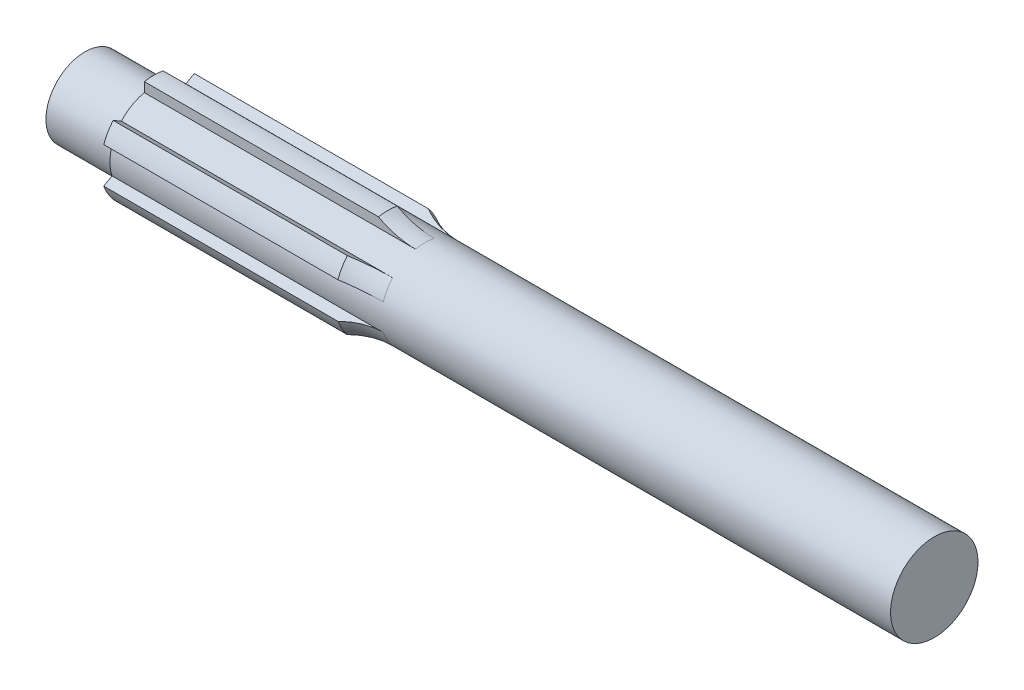
SolidWorks part; units mm, degrees
material "Gray Cast Iron"
ref_plane "Front Plane" through (0, 0, 0) normal (0, 0, 1) x (1, 0, 0)
ref_plane "Top Plane" through (0, 0, 0) normal (0, 1, 0) x (1, 0, 0)
ref_plane "Right Plane" through (0, 0, 0) normal (1, 0, 0) x (0, 0, -1)
sketch "Sketch1" plane through (0, 0, 0) normal (1, 0, 0) x (0, 0, -1)
  circle A0 centre (0, 0) radius 12.5
  dimension "D1" = 25
extrude "Boss-Extrude1" add sketch "Sketch1" along normal blind 22
sketch "Sketch2" plane through (22, 0, 0) normal (1, 0, 0) x (0, 0, -1)
  line L0 (0, -1000) -> (0, 49000) construction
  line L1 (-13.3427, -4.2393) -> (-15.9914, -5.7685)
  line L3 (-3, -13.6748) -> (-3, -16.7332)
  line L5 (3, -13.6748) -> (3, -16.7332)
  line L6 (-3, -13.6748) -> (3, -16.7332) construction
  line L7 (-3, -16.7332) -> (3, -13.6748) construction
  line L8 (-10.3427, -9.4355) -> (-12.9914, -10.9647)
  line L9 (-10.3427, 9.4355) -> (-12.9914, 10.9647)
  line L10 (-13.3427, 4.2393) -> (-15.9914, 5.7685)
  line L11 (3, 13.6748) -> (3, 16.7332)
  line L12 (-3, 13.6748) -> (-3, 16.7332)
  line L13 (13.3427, 4.2393) -> (15.9914, 5.7685)
  line L14 (10.3427, 9.4355) -> (12.9914, 10.9647)
  line L15 (10.3427, -9.4355) -> (12.9914, -10.9647)
  line L16 (13.3427, -4.2393) -> (15.9914, -5.7685)
  arc A0 (-3, 13.6748) -> (-10.3427, 9.4355) centre (0, 0) ccw
  arc A1 (3, 16.7332) -> (-3, 16.7332) centre (0, 0) ccw
  arc A2 (10.3427, 9.4355) -> (3, 13.6748) centre (0, 0) ccw
  arc A3 (15.9914, 5.7685) -> (12.9914, 10.9647) centre (0, 0) ccw
  arc A4 (13.3427, -4.2393) -> (13.3427, 4.2393) centre (0, 0) ccw
  arc A5 (12.9914, -10.9647) -> (15.9914, -5.7685) centre (0, 0) ccw
  arc A6 (3, -13.6748) -> (10.3427, -9.4355) centre (0, 0) ccw
  arc A7 (-3, -16.7332) -> (3, -16.7332) centre (0, 0) ccw
  arc A8 (-10.3427, -9.4355) -> (-3, -13.6748) centre (0, 0) ccw
  arc A9 (-15.9914, -5.7685) -> (-12.9914, -10.9647) centre (0, 0) ccw
  arc A10 (-13.3427, 4.2393) -> (-13.3427, -4.2393) centre (0, 0) ccw
  arc A11 (-12.9914, 10.9647) -> (-15.9914, 5.7685) centre (0, 0) ccw
  point P4 (0, -15.204)
  point P33 (0, 0)
  dimension "D1" = 34
  dimension "D2" = 28
  dimension "D3" = 6
  dimension "D4" = 6
sketch "Sketch3" plane through (22, 0, 0) normal (1, 0, 0) x (0, 0, -1)
  circle A0 centre (0, 0) radius 14
  dimension "D1" = 28
extrude "Boss-Extrude2" add sketch "Sketch3" along normal blind 250
extrude "Boss-Extrude3" add sketch "Sketch2" along normal blind 75
fillet "Fillet3" radius 25 6 edges at (97, 7, -12.1244) (97, -7, -12.1244) (97, -14, 0) (97, -7, 12.1244) (97, 7, 12.1244) (97, 14, 0)
